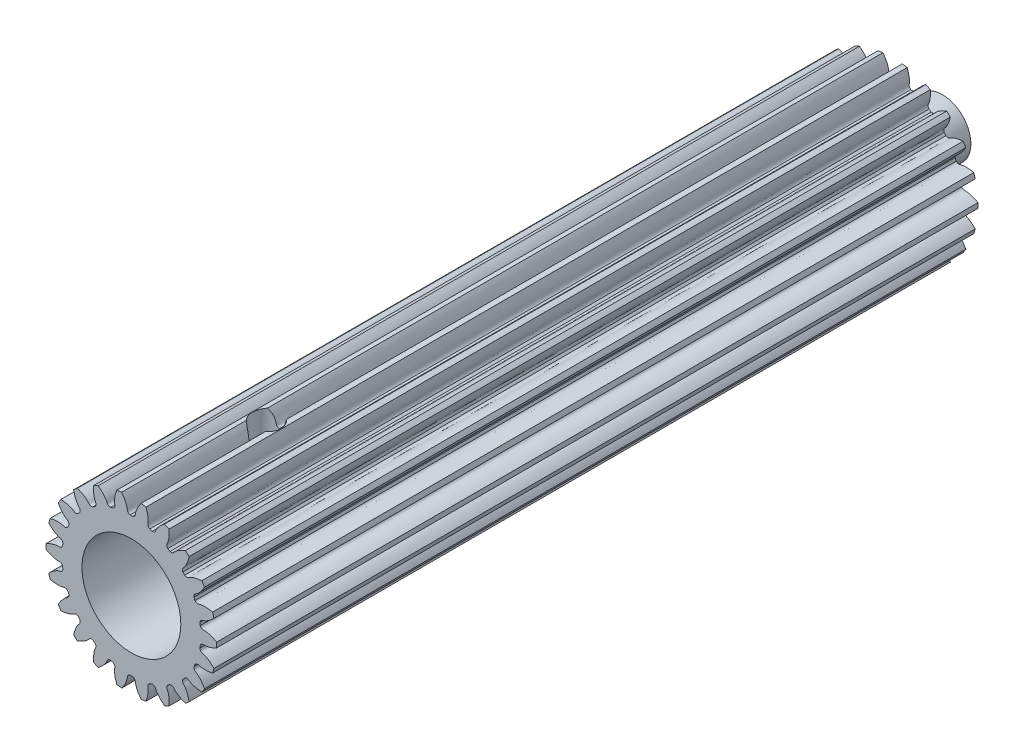
SolidWorks part; units mm, degrees
ref_plane "前视基准面" through (0, 0, 0) normal (0, 0, 1) x (1, 0, 0)
ref_plane "上视基准面" through (0, 0, 0) normal (0, 1, 0) x (1, 0, 0)
ref_plane "右视基准面" through (0, 0, 0) normal (1, 0, 0) x (0, 0, -1)
sketch "草图1" plane through (0, 0, 0) normal (0, 0, 1) x (1, 0, 0)
  circle A0 centre (0, 0) radius 12
extrude "凸台-拉伸1" add sketch "草图1" along normal blind 30
ref_axis "基准轴1" through (0, 0, -1.5) along (0, 0, 1)
sketch "草图2" plane through (0, 0, 0) normal (0, 0, 1) x (1, 0, 0)
  line L0 (0, 0) -> (0, 12) construction
  circle A0 centre (0, 0) radius 12 construction
  arc A1 (0.1857, 9.7482) -> (-0.1857, 9.7482) centre (0, 0) ccw
  arc A2 (3.0856, 13.5599) -> (-3.0856, 13.5599) centre (0, 0) ccw
  spline S0 degree 3 poles (0.1857, 9.7482) (0.5882, 9.8762) (0.5483, 10.1518) (0.5996, 10.4216) (0.606, 10.4519) (0.6139, 10.4862) (0.6235, 10.5243) (0.6349, 10.5661) (0.6484, 10.6117) (0.664, 10.661) (0.6819, 10.7139) (0.7023, 10.7703) (0.7253, 10.8301) (0.7511, 10.8933) (0.7797, 10.9597) (0.8114, 11.0293) (0.8462, 11.1021) (0.8843, 11.1778) (0.9259, 11.2563) (0.9711, 11.3377) (1.0199, 11.4217) (1.0726, 11.5082) (1.1292, 11.5972) (1.1899, 11.6884) (1.2547, 11.7818) (1.3238, 11.8773) (1.3973, 11.9746) (1.4753, 12.0737) (1.5579, 12.1744) (1.6452, 12.2766) (1.7372, 12.3802) (1.8341, 12.4849) (1.9359, 12.5906) (2.0428, 12.6972) (2.1547, 12.8044) (2.2718, 12.9123) (2.3942, 13.0205) (2.5218, 13.1289) (2.6548, 13.2373) (2.8415, 13.3834) (2.9864, 13.49) (3.0856, 13.5599) knots 0 0 0 0 0.157021 0.162531 0.168888 0.176093 0.184146 0.193046 0.202794 0.213389 0.224833 0.237123 0.250262 0.264248 0.279082 0.294763 0.311292 0.328669 0.346893 0.365965 0.385884 0.406652 0.428266 0.450729 0.474039 0.498197 0.523202 0.549055 0.575756 0.603304 0.6317 0.660944 0.691035 0.721974 0.75376 0.786395 0.819876 0.854206 0.889383 0.925408 1 1 1 1
  spline S1 degree 3 poles (-0.1857, 9.7482) (-0.5882, 9.8762) (-0.5483, 10.1518) (-0.5996, 10.4216) (-0.606, 10.4519) (-0.6139, 10.4862) (-0.6235, 10.5243) (-0.6349, 10.5661) (-0.6484, 10.6117) (-0.664, 10.661) (-0.6819, 10.7139) (-0.7023, 10.7703) (-0.7253, 10.8301) (-0.7511, 10.8933) (-0.7797, 10.9597) (-0.8114, 11.0293) (-0.8462, 11.1021) (-0.8843, 11.1778) (-0.9259, 11.2563) (-0.9711, 11.3377) (-1.0199, 11.4217) (-1.0726, 11.5082) (-1.1292, 11.5972) (-1.1899, 11.6884) (-1.2547, 11.7818) (-1.3238, 11.8773) (-1.3973, 11.9746) (-1.4753, 12.0737) (-1.5579, 12.1744) (-1.6452, 12.2766) (-1.7372, 12.3802) (-1.8341, 12.4849) (-1.9359, 12.5906) (-2.0428, 12.6972) (-2.1547, 12.8044) (-2.2718, 12.9123) (-2.3942, 13.0205) (-2.5218, 13.1289) (-2.6548, 13.2373) (-2.8415, 13.3834) (-2.9864, 13.49) (-3.0856, 13.5599) knots 0 0 0 0 0.157021 0.162531 0.168888 0.176093 0.184146 0.193046 0.202794 0.213389 0.224833 0.237123 0.250262 0.264248 0.279082 0.294763 0.311292 0.328669 0.346893 0.365965 0.385884 0.406652 0.428266 0.450729 0.474039 0.498197 0.523202 0.549055 0.575756 0.603304 0.6317 0.660944 0.691035 0.721974 0.75376 0.786395 0.819876 0.854206 0.889383 0.925408 1 1 1 1
extrude "切除-拉伸1" cut sketch "草图2" along normal through all
pattern_circular "阵列(圆周)1" count 22 every 16.364 about axis through (0, 0, -1.5) along (0, 0, 1) of "切除-拉伸1"
sketch "草图3" plane through (0, 0, 0) normal (0, 0, 1) x (1, 0, 0)
  circle A0 centre (0, 0) radius 11 construction
  dimension "Dn" = 22
sketch "草图4" plane through (0, 0, 0) normal (0, 0, -1) x (-1, 0, 0)
  arc A45 (2.9245, 9.3011) -> (2.5682, 9.4057) centre (0, 0) ccw
  arc A46 (2.0557, 11.8226) -> (1.3584, 11.9229) centre (0, 0) ccw
  arc A47 (0.1857, 9.7482) -> (-0.1857, 9.7482) centre (0, 0) ccw
  arc A48 (-1.3584, 11.9229) -> (-2.0557, 11.8226) centre (0, 0) ccw
  arc A49 (-2.5682, 9.4057) -> (-2.9245, 9.3011) centre (0, 0) ccw
  arc A50 (-4.6624, 11.0572) -> (-5.3032, 10.7646) centre (0, 0) ccw
  arc A51 (-5.1141, 8.3011) -> (-5.4265, 8.1004) centre (0, 0) ccw
  arc A52 (-7.5887, 9.2958) -> (-8.1211, 8.8344) centre (0, 0) ccw
  arc A53 (-7.2456, 6.5241) -> (-7.4888, 6.2434) centre (0, 0) ccw
  arc A54 (-9.9003, 6.7812) -> (-10.2811, 6.1886) centre (0, 0) ccw
  arc A55 (-8.7902, 4.2184) -> (-8.9444, 3.8807) centre (0, 0) ccw
  arc A56 (-11.4097, 3.7173) -> (-11.6082, 3.0414) centre (0, 0) ccw
  arc A57 (-9.6226, 1.5711) -> (-9.6754, 1.2035) centre (0, 0) ccw
  arc A58 (-11.9948, 0.3522) -> (-11.9948, -0.3522) centre (0, 0) ccw
  arc A59 (-9.6754, -1.2035) -> (-9.6226, -1.5711) centre (0, 0) ccw
  arc A60 (-11.6082, -3.0414) -> (-11.4097, -3.7173) centre (0, 0) ccw
  arc A61 (-8.9444, -3.8807) -> (-8.7902, -4.2184) centre (0, 0) ccw
  arc A62 (-10.2811, -6.1886) -> (-9.9003, -6.7812) centre (0, 0) ccw
  arc A63 (-7.4888, -6.2434) -> (-7.2456, -6.5241) centre (0, 0) ccw
  arc A64 (-8.1211, -8.8344) -> (-7.5887, -9.2958) centre (0, 0) ccw
  arc A65 (-5.4265, -8.1004) -> (-5.1141, -8.3011) centre (0, 0) ccw
  arc A66 (-5.3032, -10.7646) -> (-4.6624, -11.0572) centre (0, 0) ccw
  arc A67 (-2.9245, -9.3011) -> (-2.5682, -9.4057) centre (0, 0) ccw
  arc A68 (-2.0557, -11.8226) -> (-1.3584, -11.9229) centre (0, 0) ccw
  arc A69 (-0.1857, -9.7482) -> (0.1857, -9.7482) centre (0, 0) ccw
  arc A70 (1.3584, -11.9229) -> (2.0557, -11.8226) centre (0, 0) ccw
  arc A71 (2.5682, -9.4057) -> (2.9245, -9.3011) centre (0, 0) ccw
  arc A72 (4.6624, -11.0572) -> (5.3032, -10.7646) centre (0, 0) ccw
  arc A73 (5.1141, -8.3011) -> (5.4265, -8.1004) centre (0, 0) ccw
  arc A74 (7.5887, -9.2958) -> (8.1211, -8.8344) centre (0, 0) ccw
  arc A75 (7.2456, -6.5241) -> (7.4888, -6.2434) centre (0, 0) ccw
  arc A76 (9.9003, -6.7812) -> (10.2811, -6.1886) centre (0, 0) ccw
  arc A77 (8.7902, -4.2184) -> (8.9444, -3.8807) centre (0, 0) ccw
  arc A78 (11.4097, -3.7173) -> (11.6082, -3.0414) centre (0, 0) ccw
  arc A79 (9.6226, -1.5711) -> (9.6754, -1.2035) centre (0, 0) ccw
  arc A80 (11.9948, -0.3522) -> (11.9948, 0.3522) centre (0, 0) ccw
  arc A81 (9.6754, 1.2035) -> (9.6226, 1.5711) centre (0, 0) ccw
  arc A82 (11.6082, 3.0414) -> (11.4097, 3.7173) centre (0, 0) ccw
  arc A83 (8.9444, 3.8807) -> (8.7902, 4.2184) centre (0, 0) ccw
  arc A84 (10.2811, 6.1886) -> (9.9003, 6.7812) centre (0, 0) ccw
  arc A85 (7.4888, 6.2434) -> (7.2456, 6.5241) centre (0, 0) ccw
  arc A86 (8.1211, 8.8344) -> (7.5887, 9.2958) centre (0, 0) ccw
  arc A87 (5.4265, 8.1004) -> (5.1141, 8.3011) centre (0, 0) ccw
  arc A88 (5.3032, 10.7646) -> (4.6624, 11.0572) centre (0, 0) ccw
  arc A89 (2.9245, 9.3011) -> (2.5682, 9.4057) centre (0, 0) ccw
  arc A90 (2.0557, 11.8226) -> (1.3584, 11.9229) centre (0, 0) ccw
  arc A91 (0.1857, 9.7482) -> (-0.1857, 9.7482) centre (0, 0) ccw
  arc A92 (-1.3584, 11.9229) -> (-2.0557, 11.8226) centre (0, 0) ccw
  arc A93 (-2.5682, 9.4057) -> (-2.9245, 9.3011) centre (0, 0) ccw
  arc A94 (-4.6624, 11.0572) -> (-5.3032, 10.7646) centre (0, 0) ccw
  arc A95 (-5.1141, 8.3011) -> (-5.4265, 8.1004) centre (0, 0) ccw
  arc A96 (-7.5887, 9.2958) -> (-8.1211, 8.8344) centre (0, 0) ccw
  arc A97 (-7.2456, 6.5241) -> (-7.4888, 6.2434) centre (0, 0) ccw
  arc A98 (-9.9003, 6.7812) -> (-10.2811, 6.1886) centre (0, 0) ccw
  arc A99 (-8.7902, 4.2184) -> (-8.9444, 3.8807) centre (0, 0) ccw
  arc A100 (-11.4097, 3.7173) -> (-11.6082, 3.0414) centre (0, 0) ccw
  arc A101 (-9.6226, 1.5711) -> (-9.6754, 1.2035) centre (0, 0) ccw
  arc A102 (-11.9948, 0.3522) -> (-11.9948, -0.3522) centre (0, 0) ccw
  arc A103 (-9.6754, -1.2035) -> (-9.6226, -1.5711) centre (0, 0) ccw
  arc A104 (-11.6082, -3.0414) -> (-11.4097, -3.7173) centre (0, 0) ccw
  arc A105 (-8.9444, -3.8807) -> (-8.7902, -4.2184) centre (0, 0) ccw
  arc A106 (-10.2811, -6.1886) -> (-9.9003, -6.7812) centre (0, 0) ccw
  arc A107 (-7.4888, -6.2434) -> (-7.2456, -6.5241) centre (0, 0) ccw
  arc A108 (-8.1211, -8.8344) -> (-7.5887, -9.2958) centre (0, 0) ccw
  arc A109 (-5.4265, -8.1004) -> (-5.1141, -8.3011) centre (0, 0) ccw
  arc A110 (-5.3032, -10.7646) -> (-4.6624, -11.0572) centre (0, 0) ccw
  arc A111 (-2.9245, -9.3011) -> (-2.5682, -9.4057) centre (0, 0) ccw
  arc A112 (-2.0557, -11.8226) -> (-1.3584, -11.9229) centre (0, 0) ccw
  arc A113 (-0.1857, -9.7482) -> (0.1857, -9.7482) centre (0, 0) ccw
  arc A114 (1.3584, -11.9229) -> (2.0557, -11.8226) centre (0, 0) ccw
  arc A115 (2.5682, -9.4057) -> (2.9245, -9.3011) centre (0, 0) ccw
  arc A116 (4.6624, -11.0572) -> (5.3032, -10.7646) centre (0, 0) ccw
  arc A117 (5.1141, -8.3011) -> (5.4265, -8.1004) centre (0, 0) ccw
  arc A118 (7.5887, -9.2958) -> (8.1211, -8.8344) centre (0, 0) ccw
  arc A119 (7.2456, -6.5241) -> (7.4888, -6.2434) centre (0, 0) ccw
  arc A120 (9.9003, -6.7812) -> (10.2811, -6.1886) centre (0, 0) ccw
  arc A121 (8.7902, -4.2184) -> (8.9444, -3.8807) centre (0, 0) ccw
  arc A122 (11.4097, -3.7173) -> (11.6082, -3.0414) centre (0, 0) ccw
  arc A123 (9.6226, -1.5711) -> (9.6754, -1.2035) centre (0, 0) ccw
  arc A124 (11.9948, -0.3522) -> (11.9948, 0.3522) centre (0, 0) ccw
  arc A125 (9.6754, 1.2035) -> (9.6226, 1.5711) centre (0, 0) ccw
  arc A126 (11.6082, 3.0414) -> (11.4097, 3.7173) centre (0, 0) ccw
  arc A127 (8.9444, 3.8807) -> (8.7902, 4.2184) centre (0, 0) ccw
  arc A128 (10.2811, 6.1886) -> (9.9003, 6.7812) centre (0, 0) ccw
  arc A129 (7.4888, 6.2434) -> (7.2456, 6.5241) centre (0, 0) ccw
  arc A130 (8.1211, 8.8344) -> (7.5887, 9.2958) centre (0, 0) ccw
  arc A131 (5.4265, 8.1004) -> (5.1141, 8.3011) centre (0, 0) ccw
  arc A132 (5.3032, 10.7646) -> (4.6624, 11.0572) centre (0, 0) ccw
  spline S44 degree 3 poles (-6562.0363, 2433.3447) (210.1462, -143.3518) (27.5625, 30.6747) (4.2738, 10.7434) (4.1283, 10.6084) (3.9999, 10.4794) (3.888, 10.3576) (3.7917, 10.2441) (3.7102, 10.1398) (3.6518, 10.0587) (3.6037, 9.9872) (3.5713, 9.9359) (3.5381, 9.8795) (3.5167, 9.8409) (0.7608, 4.4593) (40.1108, -21.8996) (-5890.5321, 3783.681) knots -18.214825 -18.214825 -18.214825 -18.214825 0.549271 0.593348 0.634035 0.671331 0.705237 0.735752 0.762877 0.786611 0.797206 0.815854 0.823907 0.837469 0.842979 4.542303 4.542303 4.542303 4.542303 only from (4.6624, 11.0572) to (2.9245, 9.3011)
  spline S45 degree 3 poles (6999.9868, -1.6264) (-45.5784, 3.2625) (1.7708, 4.163) (2.3619, 10.18) (2.3658, 10.2385) (2.3681, 10.3211) (2.3668, 10.4204) (2.3608, 10.536) (2.3486, 10.6678) (2.329, 10.8154) (2.3007, 10.9784) (2.2624, 11.1562) (2.213, 11.3485) (2.1511, 11.5544) (-8.4551, 42.3513) (-266.8007, -17.8123) (6842.6381, -1469.6189) knots -3.542118 -3.542118 -3.542118 -3.542118 0.157021 0.162531 0.176093 0.193046 0.213389 0.237123 0.264248 0.294763 0.328669 0.365965 0.406652 0.450729 0.498197 20.435356 20.435356 20.435356 20.435356 only from (2.5682, 9.4057) to (2.0557, 11.8226)
  spline S46 degree 3 poles (-6981.7801, 486.0379) (242.0207, -78.34) (17.804, 37.1975) (1.0739, 11.5123) (0.9723, 11.3417) (0.8855, 11.1818) (0.8124, 11.0334) (0.752, 10.8973) (0.7032, 10.7743) (0.6701, 10.6801) (0.644, 10.5979) (0.6274, 10.5396) (0.6113, 10.4761) (0.6018, 10.4331) (-0.5263, 4.493) (44.6558, -9.712) (-6717.9103, 1970.8607) knots -18.214825 -18.214825 -18.214825 -18.214825 0.549271 0.593348 0.634035 0.671331 0.705237 0.735752 0.762877 0.786611 0.797206 0.815854 0.823907 0.837469 0.842979 4.542303 4.542303 4.542303 4.542303 only from (1.3584, 11.9229) to (0.1857, 9.7482)
  spline S47 degree 3 poles (6716.8964, 1970.5637) (-44.6513, -9.7106) (0.5262, 4.4933) (-0.6018, 10.4331) (-0.6145, 10.4903) (-0.6356, 10.5702) (-0.6648, 10.6651) (-0.7032, 10.7743) (-0.752, 10.8973) (-0.8124, 11.0334) (-0.8855, 11.1818) (-0.9723, 11.3417) (-1.0739, 11.5123) (-1.1913, 11.6924) (-20.0444, 38.2537) (-250.9751, -92.2573) (6979.5027, 517.7049) knots -3.542118 -3.542118 -3.542118 -3.542118 0.157021 0.162531 0.176093 0.193046 0.213389 0.237123 0.264248 0.294763 0.328669 0.365965 0.406652 0.450729 0.498197 20.435356 20.435356 20.435356 20.435356 only from (-0.1857, 9.7482) to (-1.3584, 11.9229)
  spline S48 degree 3 poles (-6835.9017, -1500.6448) (254.2881, -6.9816) (6.6031, 40.7067) (-2.213, 11.3485) (-2.2624, 11.1562) (-2.3007, 10.9784) (-2.329, 10.8154) (-2.3486, 10.6678) (-2.3608, 10.536) (-2.366, 10.4362) (-2.3678, 10.3501) (-2.3674, 10.2894) (-2.3649, 10.224) (-2.3619, 10.18) (-1.7708, 4.1627) (45.5832, 3.2624) (-7001.0433, -1.6271) knots -18.214825 -18.214825 -18.214825 -18.214825 0.549271 0.593348 0.634035 0.671331 0.705237 0.735752 0.762877 0.786611 0.797206 0.815854 0.823907 0.837469 0.842979 4.542303 4.542303 4.542303 4.542303 only from (-2.0557, 11.8226) to (-2.5682, 9.4057)
  spline S49 degree 3 poles (5889.6429, 3783.1104) (-40.1068, -21.897) (-0.761, 4.4596) (-3.5167, 9.8409) (-3.5451, 9.8922) (-3.5879, 9.963) (-3.6426, 10.0458) (-3.7102, 10.1398) (-3.7917, 10.2441) (-3.888, 10.3576) (-3.9999, 10.4794) (-4.1283, 10.6084) (-4.2738, 10.7434) (-4.4372, 10.8832) (-30.0098, 31.057) (-214.817, -159.2281) (6550.9294, 2463.0873) knots -3.542118 -3.542118 -3.542118 -3.542118 0.157021 0.162531 0.176093 0.193046 0.213389 0.237123 0.264248 0.294763 0.328669 0.365965 0.406652 0.450729 0.498197 20.435356 20.435356 20.435356 20.435356 only from (-2.9245, 9.3011) to (-4.6624, 11.0572)
  spline S50 degree 3 poles (-6136.2191, -3365.7542) (245.9546, 64.9425) (-5.1328, 40.918) (-5.3206, 10.2653) (-5.3138, 10.0669) (-5.3004, 9.8855) (-5.2817, 9.7211) (-5.2589, 9.574) (-5.2335, 9.4441) (-5.2104, 9.3469) (-5.1879, 9.2637) (-5.1704, 9.2057) (-5.1495, 9.1436) (-5.1343, 9.1022) (-2.8719, 3.4952) (42.8176, 15.9725) (-6716.9935, -1973.983) knots -18.214825 -18.214825 -18.214825 -18.214825 0.549271 0.593348 0.634035 0.671331 0.705237 0.735752 0.762877 0.786611 0.797206 0.815854 0.823907 0.837469 0.842979 4.542303 4.542303 4.542303 4.542303 only from (-5.3032, 10.7646) to (-5.1141, 8.3011)
  spline S51 degree 3 poles (4585.2456, 5289.172) (-32.3131, -32.3094) (-1.9866, 4.0645) (-6.1468, 8.4515) (-6.1884, 8.4928) (-6.2494, 8.5486) (-6.3253, 8.6126) (-6.4166, 8.6838) (-6.5242, 8.7609) (-6.6486, 8.8427) (-6.7903, 8.928) (-6.9498, 9.0156) (-7.1274, 9.1041) (-7.3236, 9.1923) (-37.5439, 21.3442) (-161.2557, -213.2991) (5591.6389, 4208.9251) knots -3.542118 -3.542118 -3.542118 -3.542118 0.157021 0.162531 0.176093 0.193046 0.213389 0.237123 0.264248 0.294763 0.328669 0.365965 0.406652 0.450729 0.498197 20.435356 20.435356 20.435356 20.435356 only from (-5.4265, 8.1004) to (-7.5887, 9.2958)
  spline S52 degree 3 poles (-4939.4166, -4958.1902) (217.6953, 131.6052) (-16.4528, 37.8145) (-7.9971, 8.3505) (-7.9348, 8.1621) (-7.8708, 7.9917) (-7.8065, 7.8393) (-7.7432, 7.7046) (-7.6822, 7.5871) (-7.6327, 7.5003) (-7.5876, 7.4269) (-7.5545, 7.3761) (-7.517, 7.3224) (-7.4907, 7.287) (-3.7403, 2.5445) (36.5832, 27.3886) (-5888.7728, -3786.4186) knots -18.214825 -18.214825 -18.214825 -18.214825 0.549271 0.593348 0.634035 0.671331 0.705237 0.735752 0.762877 0.786611 0.797206 0.815854 0.823907 0.837469 0.842979 4.542303 4.542303 4.542303 4.542303 only from (-8.1211, 8.8344) to (-7.2456, 6.5241)
  spline S53 degree 3 poles (2909.379, 6366.7364) (-21.9016, -40.1043) (-3.0512, 3.3402) (-8.2789, 6.3774) (-8.3304, 6.4053) (-8.4047, 6.4416) (-8.4955, 6.4817) (-8.6032, 6.5243) (-8.7281, 6.5679) (-8.8705, 6.6114) (-9.0305, 6.6533) (-9.2082, 6.6924) (-9.4036, 6.7273) (-9.6167, 6.7566) (-42.0365, 9.9023) (-94.6304, -250.09) (4179.347, 5613.7808) knots -3.542118 -3.542118 -3.542118 -3.542118 0.157021 0.162531 0.176093 0.193046 0.213389 0.237123 0.264248 0.294763 0.328669 0.365965 0.406652 0.450729 0.498197 20.435356 20.435356 20.435356 20.435356 only from (-7.4888, 6.2434) to (-9.9003, 6.7812)
  spline S54 degree 3 poles (-3342.4519, -6148.9431) (171.7996, 187.6062) (-26.44, 31.6475) (-10.0258, 5.7592) (-9.9129, 5.596) (-9.8035, 5.4506) (-9.6989, 5.3224) (-9.6002, 5.211) (-9.5086, 5.1155) (-9.4366, 5.0462) (-9.3727, 4.9884) (-9.3266, 4.949) (-9.2755, 4.908) (-9.2403, 4.8814) (-4.3056, 1.3877) (27.3851, 36.5859) (-4583.4787, -5292.101) knots -18.214825 -18.214825 -18.214825 -18.214825 0.549271 0.593348 0.634035 0.671331 0.705237 0.735752 0.762877 0.786611 0.797206 0.815854 0.823907 0.837469 0.842979 4.542303 4.542303 4.542303 4.542303 only from (-10.2811, 6.1886) to (-8.7902, 4.2184)
  spline S55 degree 3 poles (997.8118, 6928.5056) (-9.7158, -44.6502) (-3.8686, 2.3453) (-9.7402, 3.7867) (-9.7976, 3.7989) (-9.8791, 3.8128) (-9.9775, 3.8257) (-10.0928, 3.8362) (-10.225, 3.8429) (-10.3738, 3.8445) (-10.5392, 3.8396) (-10.7207, 3.8271) (-10.918, 3.8055) (-11.1307, 3.7736) (-43.1235, -2.3419) (-20.3387, -266.62) (2428.4693, 6563.8413) knots -3.542118 -3.542118 -3.542118 -3.542118 0.157021 0.162531 0.176093 0.193046 0.213389 0.237123 0.264248 0.294763 0.328669 0.365965 0.406652 0.450729 0.498197 20.435356 20.435356 20.435356 20.435356 only from (-8.9444, 3.8807) to (-11.4097, 3.7173)
  spline S56 degree 3 poles (-1474.7016, -6841.5453) (111.9857, 228.4083) (-34.2851, 22.9165) (-11.2422, 2.7013) (-11.0879, 2.5765) (-10.942, 2.4678) (-10.8055, 2.3743) (-10.6794, 2.2952) (-10.5646, 2.2294) (-10.476, 2.1832) (-10.3984, 2.1457) (-10.3431, 2.1209) (-10.2825, 2.096) (-10.2412, 2.0804) (-4.5222, 0.1185) (15.9684, 42.8191) (-2906.8585, -6369.0489) knots -18.214825 -18.214825 -18.214825 -18.214825 0.549271 0.593348 0.634035 0.671331 0.705237 0.735752 0.762877 0.786611 0.797206 0.815854 0.823907 0.837469 0.842979 4.542303 4.542303 4.542303 4.542303 only from (-11.6082, 3.0414) to (-9.6226, 1.5711)
  spline S57 degree 3 poles (-994.5922, 6928.9685) (3.2572, -45.5788) (-4.3727, 1.1604) (-10.4125, 0.8891) (-10.4709, 0.8847) (-10.5531, 0.8751) (-10.6512, 0.8598) (-10.7647, 0.8373) (-10.8934, 0.8065) (-11.0367, 0.7661) (-11.194, 0.7149) (-11.3647, 0.6517) (-11.5479, 0.5754) (-11.743, 0.4849) (-40.717, -14.3963) (55.6007, -261.5501) (480.8514, 6982.1385) knots -3.542118 -3.542118 -3.542118 -3.542118 0.157021 0.162531 0.176093 0.193046 0.213389 0.237123 0.264248 0.294763 0.328669 0.365965 0.406652 0.450729 0.498197 20.435356 20.435356 20.435356 20.435356 only from (-9.6754, 1.2035) to (-11.9948, 0.3522)
  spline S58 degree 3 poles (512.5202, -6979.8861) (43.0995, 250.7062) (-39.3526, 12.329) (-11.5479, -0.5754) (-11.3647, -0.6517) (-11.194, -0.7149) (-11.0367, -0.7661) (-10.8934, -0.8065) (-10.7647, -0.8373) (-10.6667, -0.8567) (-10.5817, -0.8708) (-10.5216, -0.879) (-10.4565, -0.8858) (-10.4125, -0.8891) (-4.3724, -1.1604) (3.258, 45.5835) (-994.7418, -6930.0144) knots -18.214825 -18.214825 -18.214825 -18.214825 0.549271 0.593348 0.634035 0.671331 0.705237 0.735752 0.762877 0.786611 0.797206 0.815854 0.823907 0.837469 0.842979 4.542303 4.542303 4.542303 4.542303 only from (-11.9948, -0.3522) to (-9.6754, -1.2035)
  spline S59 degree 3 poles (-2906.4202, 6368.0876) (15.9663, -42.8149) (-4.5225, -0.1186) (-10.2412, -2.0804) (-10.296, -2.1012) (-10.3722, -2.1335) (-10.4619, -2.1758) (-10.5646, -2.2294) (-10.6794, -2.2952) (-10.8055, -2.3743) (-10.942, -2.4678) (-11.0879, -2.5765) (-11.2422, -2.7014) (-11.4039, -2.8432) (-35.0117, -25.2845) (127.0357, -235.291) (-1505.7222, 6834.7843) knots -3.542118 -3.542118 -3.542118 -3.542118 0.157021 0.162531 0.176093 0.193046 0.213389 0.237123 0.264248 0.294763 0.328669 0.365965 0.406652 0.450729 0.498197 20.435356 20.435356 20.435356 20.435356 only from (-9.6226, -1.5711) to (-11.6082, -3.0414)
  spline S60 degree 3 poles (2458.2207, -6552.758) (-29.2785, 252.6934) (-41.232, 0.7427) (-10.918, -3.8055) (-10.7207, -3.8271) (-10.5392, -3.8396) (-10.3738, -3.8445) (-10.225, -3.8429) (-10.0928, -3.8362) (-9.9933, -3.8272) (-9.9078, -3.8167) (-9.8478, -3.8076) (-9.7834, -3.7958) (-9.7402, -3.7867) (-3.8684, -2.3452) (-9.7163, 44.6549) (997.9629, -6929.5512) knots -18.214825 -18.214825 -18.214825 -18.214825 0.549271 0.593348 0.634035 0.671331 0.705237 0.735752 0.762877 0.786611 0.797206 0.815854 0.823907 0.837469 0.842979 4.542303 4.542303 4.542303 4.542303 only from (-11.4097, -3.7173) to (-8.9444, -3.8807)
  spline S61 degree 3 poles (-4582.7874, 5291.3021) (27.3819, -36.5824) (-4.3059, -1.3879) (-9.2403, -4.8814) (-9.287, -4.9168) (-9.351, -4.9692) (-9.4251, -5.0352) (-9.5086, -5.1155) (-9.6002, -5.211) (-9.6989, -5.3224) (-9.8035, -5.4506) (-9.9129, -5.596) (-10.0258, -5.7592) (-10.1409, -5.9408) (-26.4701, -34.1242) (188.179, -189.9699) (-3370.3111, 6133.7165) knots -3.542118 -3.542118 -3.542118 -3.542118 0.157021 0.162531 0.176093 0.193046 0.213389 0.237123 0.264248 0.294763 0.328669 0.365965 0.406652 0.450729 0.498197 20.435356 20.435356 20.435356 20.435356 only from (-8.7902, -4.2184) to (-10.2811, -6.1886)
  spline S62 degree 3 poles (4204.7707, -5594.7645) (-99.2844, 234.2088) (-39.7711, -10.9038) (-9.4036, -6.7273) (-9.2082, -6.6924) (-9.0305, -6.6533) (-8.8705, -6.6114) (-8.7281, -6.5679) (-8.6032, -6.5243) (-8.5102, -6.4876) (-8.4311, -6.4535) (-8.3761, -6.4279) (-8.3177, -6.3984) (-8.2789, -6.3774) (-3.0509, -3.3401) (-21.9035, 40.1087) (2909.8186, -6367.6971) knots -18.214825 -18.214825 -18.214825 -18.214825 0.549271 0.593348 0.634035 0.671331 0.705237 0.735752 0.762877 0.786611 0.797206 0.815854 0.823907 0.837469 0.842979 4.542303 4.542303 4.542303 4.542303 only from (-9.9003, -6.7812) to (-7.4888, -6.2434)
  spline S63 degree 3 poles (-5887.8844, 3785.8468) (36.5792, -27.3861) (-3.7404, -2.5448) (-7.4907, -7.287) (-7.5256, -7.3341) (-7.5722, -7.4024) (-7.6248, -7.4866) (-7.6822, -7.5871) (-7.7432, -7.7046) (-7.8065, -7.8393) (-7.8708, -7.9917) (-7.9348, -8.1621) (-7.9971, -8.3505) (-8.0564, -8.5572) (-15.7839, -40.1994) (234.0771, -129.2587) (-4961.8575, 4935.7316) knots -3.542118 -3.542118 -3.542118 -3.542118 0.157021 0.162531 0.176093 0.193046 0.213389 0.237123 0.264248 0.294763 0.328669 0.365965 0.406652 0.450729 0.498197 20.435356 20.435356 20.435356 20.435356 only from (-7.2456, -6.5241) to (-8.1211, -8.8344)
  spline S64 degree 3 poles (5610.6753, -4183.5164) (-161.247, 196.7501) (-35.0881, -21.6669) (-7.1274, -9.1041) (-6.9498, -9.0156) (-6.7903, -8.928) (-6.6486, -8.8427) (-6.5242, -8.7609) (-6.4166, -8.6838) (-6.3378, -8.6224) (-6.2715, -8.5674) (-6.2259, -8.5273) (-6.1781, -8.4826) (-6.1468, -8.4515) (-1.9864, -4.0643) (-32.3162, 32.313) (4585.938, -5289.97) knots -18.214825 -18.214825 -18.214825 -18.214825 0.549271 0.593348 0.634035 0.671331 0.705237 0.735752 0.762877 0.786611 0.797206 0.815854 0.823907 0.837469 0.842979 4.542303 4.542303 4.542303 4.542303 only from (-7.5887, -9.2958) to (-5.4265, -8.1004)
  spline S65 degree 3 poles (-6715.98, 1973.6847) (42.813, -15.9713) (-2.872, -3.4955) (-5.1343, -9.1022) (-5.1545, -9.1572) (-5.18, -9.2359) (-5.2067, -9.3315) (-5.2335, -9.4441) (-5.2589, -9.574) (-5.2817, -9.7211) (-5.3004, -9.8855) (-5.3138, -10.0669) (-5.3206, -10.2653) (-5.3192, -10.4804) (-3.8191, -43.0179) (261.0117, -58.0756) (-6151.4237, 3337.8829) knots -3.542118 -3.542118 -3.542118 -3.542118 0.157021 0.162531 0.176093 0.193046 0.213389 0.237123 0.264248 0.294763 0.328669 0.365965 0.406652 0.450729 0.498197 20.435356 20.435356 20.435356 20.435356 only from (-5.1141, -8.3011) to (-5.3032, -10.7646)
  spline S66 degree 3 poles (6562.0363, -2433.3447) (-210.1462, 143.3518) (-27.5625, -30.6747) (-4.2738, -10.7434) (-4.1283, -10.6084) (-3.9999, -10.4794) (-3.888, -10.3576) (-3.7917, -10.2441) (-3.7102, -10.1398) (-3.6518, -10.0587) (-3.6037, -9.9872) (-3.5713, -9.9359) (-3.5381, -9.8795) (-3.5167, -9.8409) (-0.7608, -4.4593) (-40.1108, 21.8996) (5890.5321, -3783.681) knots -18.214825 -18.214825 -18.214825 -18.214825 0.549271 0.593348 0.634035 0.671331 0.705237 0.735752 0.762877 0.786611 0.797206 0.815854 0.823907 0.837469 0.842979 4.542303 4.542303 4.542303 4.542303 only from (-4.6624, -11.0572) to (-2.9245, -9.3011)
  spline S67 degree 3 poles (-6999.9868, 1.6264) (45.5784, -3.2625) (-1.7708, -4.163) (-2.3619, -10.18) (-2.3658, -10.2385) (-2.3681, -10.3211) (-2.3668, -10.4204) (-2.3608, -10.536) (-2.3486, -10.6678) (-2.329, -10.8154) (-2.3007, -10.9784) (-2.2624, -11.1562) (-2.213, -11.3485) (-2.1511, -11.5544) (8.4551, -42.3513) (266.8007, 17.8123) (-6842.6381, 1469.6189) knots -3.542118 -3.542118 -3.542118 -3.542118 0.157021 0.162531 0.176093 0.193046 0.213389 0.237123 0.264248 0.294763 0.328669 0.365965 0.406652 0.450729 0.498197 20.435356 20.435356 20.435356 20.435356 only from (-2.5682, -9.4057) to (-2.0557, -11.8226)
  spline S68 degree 3 poles (6981.7801, -486.0379) (-242.0207, 78.34) (-17.804, -37.1975) (-1.0739, -11.5123) (-0.9723, -11.3417) (-0.8855, -11.1818) (-0.8124, -11.0334) (-0.752, -10.8973) (-0.7032, -10.7743) (-0.6701, -10.6801) (-0.644, -10.5979) (-0.6274, -10.5396) (-0.6113, -10.4761) (-0.6018, -10.4331) (0.5263, -4.493) (-44.6558, 9.712) (6717.9103, -1970.8607) knots -18.214825 -18.214825 -18.214825 -18.214825 0.549271 0.593348 0.634035 0.671331 0.705237 0.735752 0.762877 0.786611 0.797206 0.815854 0.823907 0.837469 0.842979 4.542303 4.542303 4.542303 4.542303 only from (-1.3584, -11.9229) to (-0.1857, -9.7482)
  spline S69 degree 3 poles (-6716.8964, -1970.5637) (44.6513, 9.7106) (-0.5262, -4.4933) (0.6018, -10.4331) (0.6145, -10.4903) (0.6356, -10.5702) (0.6648, -10.6651) (0.7032, -10.7743) (0.752, -10.8973) (0.8124, -11.0334) (0.8855, -11.1818) (0.9723, -11.3417) (1.0739, -11.5123) (1.1913, -11.6924) (20.0444, -38.2537) (250.9751, 92.2573) (-6979.5027, -517.7049) knots -3.542118 -3.542118 -3.542118 -3.542118 0.157021 0.162531 0.176093 0.193046 0.213389 0.237123 0.264248 0.294763 0.328669 0.365965 0.406652 0.450729 0.498197 20.435356 20.435356 20.435356 20.435356 only from (0.1857, -9.7482) to (1.3584, -11.9229)
  spline S70 degree 3 poles (6835.9017, 1500.6448) (-254.2881, 6.9816) (-6.6031, -40.7067) (2.213, -11.3485) (2.2624, -11.1562) (2.3007, -10.9784) (2.329, -10.8154) (2.3486, -10.6678) (2.3608, -10.536) (2.366, -10.4362) (2.3678, -10.3501) (2.3674, -10.2894) (2.3649, -10.224) (2.3619, -10.18) (1.7708, -4.1627) (-45.5832, -3.2624) (7001.0433, 1.6271) knots -18.214825 -18.214825 -18.214825 -18.214825 0.549271 0.593348 0.634035 0.671331 0.705237 0.735752 0.762877 0.786611 0.797206 0.815854 0.823907 0.837469 0.842979 4.542303 4.542303 4.542303 4.542303 only from (2.0557, -11.8226) to (2.5682, -9.4057)
  spline S71 degree 3 poles (-5889.6429, -3783.1104) (40.1068, 21.897) (0.761, -4.4596) (3.5167, -9.8409) (3.5451, -9.8922) (3.5879, -9.963) (3.6426, -10.0458) (3.7102, -10.1398) (3.7917, -10.2441) (3.888, -10.3576) (3.9999, -10.4794) (4.1283, -10.6084) (4.2738, -10.7434) (4.4372, -10.8832) (30.0098, -31.057) (214.817, 159.2281) (-6550.9294, -2463.0873) knots -3.542118 -3.542118 -3.542118 -3.542118 0.157021 0.162531 0.176093 0.193046 0.213389 0.237123 0.264248 0.294763 0.328669 0.365965 0.406652 0.450729 0.498197 20.435356 20.435356 20.435356 20.435356 only from (2.9245, -9.3011) to (4.6624, -11.0572)
  spline S72 degree 3 poles (6136.2191, 3365.7542) (-245.9546, -64.9425) (5.1328, -40.918) (5.3206, -10.2653) (5.3138, -10.0669) (5.3004, -9.8855) (5.2817, -9.7211) (5.2589, -9.574) (5.2335, -9.4441) (5.2104, -9.3469) (5.1879, -9.2637) (5.1704, -9.2057) (5.1495, -9.1436) (5.1343, -9.1022) (2.8719, -3.4952) (-42.8176, -15.9725) (6716.9935, 1973.983) knots -18.214825 -18.214825 -18.214825 -18.214825 0.549271 0.593348 0.634035 0.671331 0.705237 0.735752 0.762877 0.786611 0.797206 0.815854 0.823907 0.837469 0.842979 4.542303 4.542303 4.542303 4.542303 only from (5.3032, -10.7646) to (5.1141, -8.3011)
  spline S73 degree 3 poles (-4585.2456, -5289.172) (32.3131, 32.3094) (1.9866, -4.0645) (6.1468, -8.4515) (6.1884, -8.4928) (6.2494, -8.5486) (6.3253, -8.6126) (6.4166, -8.6838) (6.5242, -8.7609) (6.6486, -8.8427) (6.7903, -8.928) (6.9498, -9.0156) (7.1274, -9.1041) (7.3236, -9.1923) (37.5439, -21.3442) (161.2557, 213.2991) (-5591.6389, -4208.9251) knots -3.542118 -3.542118 -3.542118 -3.542118 0.157021 0.162531 0.176093 0.193046 0.213389 0.237123 0.264248 0.294763 0.328669 0.365965 0.406652 0.450729 0.498197 20.435356 20.435356 20.435356 20.435356 only from (5.4265, -8.1004) to (7.5887, -9.2958)
  spline S74 degree 3 poles (4939.4166, 4958.1902) (-217.6953, -131.6052) (16.4528, -37.8145) (7.9971, -8.3505) (7.9348, -8.1621) (7.8708, -7.9917) (7.8065, -7.8393) (7.7432, -7.7046) (7.6822, -7.5871) (7.6327, -7.5003) (7.5876, -7.4269) (7.5545, -7.3761) (7.517, -7.3224) (7.4907, -7.287) (3.7403, -2.5445) (-36.5832, -27.3886) (5888.7728, 3786.4186) knots -18.214825 -18.214825 -18.214825 -18.214825 0.549271 0.593348 0.634035 0.671331 0.705237 0.735752 0.762877 0.786611 0.797206 0.815854 0.823907 0.837469 0.842979 4.542303 4.542303 4.542303 4.542303 only from (8.1211, -8.8344) to (7.2456, -6.5241)
  spline S75 degree 3 poles (-2909.379, -6366.7364) (21.9016, 40.1043) (3.0512, -3.3402) (8.2789, -6.3774) (8.3304, -6.4053) (8.4047, -6.4416) (8.4955, -6.4817) (8.6032, -6.5243) (8.7281, -6.5679) (8.8705, -6.6114) (9.0305, -6.6533) (9.2082, -6.6924) (9.4036, -6.7273) (9.6167, -6.7566) (42.0365, -9.9023) (94.6304, 250.09) (-4179.347, -5613.7808) knots -3.542118 -3.542118 -3.542118 -3.542118 0.157021 0.162531 0.176093 0.193046 0.213389 0.237123 0.264248 0.294763 0.328669 0.365965 0.406652 0.450729 0.498197 20.435356 20.435356 20.435356 20.435356 only from (7.4888, -6.2434) to (9.9003, -6.7812)
  spline S76 degree 3 poles (3342.4519, 6148.9431) (-171.7996, -187.6062) (26.44, -31.6475) (10.0258, -5.7592) (9.9129, -5.596) (9.8035, -5.4506) (9.6989, -5.3224) (9.6002, -5.211) (9.5086, -5.1155) (9.4366, -5.0462) (9.3727, -4.9884) (9.3266, -4.949) (9.2755, -4.908) (9.2403, -4.8814) (4.3056, -1.3877) (-27.3851, -36.5859) (4583.4787, 5292.101) knots -18.214825 -18.214825 -18.214825 -18.214825 0.549271 0.593348 0.634035 0.671331 0.705237 0.735752 0.762877 0.786611 0.797206 0.815854 0.823907 0.837469 0.842979 4.542303 4.542303 4.542303 4.542303 only from (10.2811, -6.1886) to (8.7902, -4.2184)
  spline S77 degree 3 poles (-997.8118, -6928.5056) (9.7158, 44.6502) (3.8686, -2.3453) (9.7402, -3.7867) (9.7976, -3.7989) (9.8791, -3.8128) (9.9775, -3.8257) (10.0928, -3.8362) (10.225, -3.8429) (10.3738, -3.8445) (10.5392, -3.8396) (10.7207, -3.8271) (10.918, -3.8055) (11.1307, -3.7736) (43.1235, 2.3419) (20.3387, 266.62) (-2428.4693, -6563.8413) knots -3.542118 -3.542118 -3.542118 -3.542118 0.157021 0.162531 0.176093 0.193046 0.213389 0.237123 0.264248 0.294763 0.328669 0.365965 0.406652 0.450729 0.498197 20.435356 20.435356 20.435356 20.435356 only from (8.9444, -3.8807) to (11.4097, -3.7173)
  spline S78 degree 3 poles (1474.7016, 6841.5453) (-111.9857, -228.4083) (34.2851, -22.9165) (11.2422, -2.7013) (11.0879, -2.5765) (10.942, -2.4678) (10.8055, -2.3743) (10.6794, -2.2952) (10.5646, -2.2294) (10.476, -2.1832) (10.3984, -2.1457) (10.3431, -2.1209) (10.2825, -2.096) (10.2412, -2.0804) (4.5222, -0.1185) (-15.9684, -42.8191) (2906.8585, 6369.0489) knots -18.214825 -18.214825 -18.214825 -18.214825 0.549271 0.593348 0.634035 0.671331 0.705237 0.735752 0.762877 0.786611 0.797206 0.815854 0.823907 0.837469 0.842979 4.542303 4.542303 4.542303 4.542303 only from (11.6082, -3.0414) to (9.6226, -1.5711)
  spline S79 degree 3 poles (994.5922, -6928.9685) (-3.2572, 45.5788) (4.3727, -1.1604) (10.4125, -0.8891) (10.4709, -0.8847) (10.5531, -0.8751) (10.6512, -0.8598) (10.7647, -0.8373) (10.8934, -0.8065) (11.0367, -0.7661) (11.194, -0.7149) (11.3647, -0.6517) (11.5479, -0.5754) (11.743, -0.4849) (40.717, 14.3963) (-55.6007, 261.5501) (-480.8514, -6982.1385) knots -3.542118 -3.542118 -3.542118 -3.542118 0.157021 0.162531 0.176093 0.193046 0.213389 0.237123 0.264248 0.294763 0.328669 0.365965 0.406652 0.450729 0.498197 20.435356 20.435356 20.435356 20.435356 only from (9.6754, -1.2035) to (11.9948, -0.3522)
  spline S80 degree 3 poles (-512.5202, 6979.8861) (-43.0995, -250.7062) (39.3526, -12.329) (11.5479, 0.5754) (11.3647, 0.6517) (11.194, 0.7149) (11.0367, 0.7661) (10.8934, 0.8065) (10.7647, 0.8373) (10.6667, 0.8567) (10.5817, 0.8708) (10.5216, 0.879) (10.4565, 0.8858) (10.4125, 0.8891) (4.3724, 1.1604) (-3.258, -45.5835) (994.7418, 6930.0144) knots -18.214825 -18.214825 -18.214825 -18.214825 0.549271 0.593348 0.634035 0.671331 0.705237 0.735752 0.762877 0.786611 0.797206 0.815854 0.823907 0.837469 0.842979 4.542303 4.542303 4.542303 4.542303 only from (11.9948, 0.3522) to (9.6754, 1.2035)
  spline S81 degree 3 poles (2906.4202, -6368.0876) (-15.9663, 42.8149) (4.5225, 0.1186) (10.2412, 2.0804) (10.296, 2.1012) (10.3722, 2.1335) (10.4619, 2.1758) (10.5646, 2.2294) (10.6794, 2.2952) (10.8055, 2.3743) (10.942, 2.4678) (11.0879, 2.5765) (11.2422, 2.7014) (11.4039, 2.8432) (35.0117, 25.2845) (-127.0357, 235.291) (1505.7222, -6834.7843) knots -3.542118 -3.542118 -3.542118 -3.542118 0.157021 0.162531 0.176093 0.193046 0.213389 0.237123 0.264248 0.294763 0.328669 0.365965 0.406652 0.450729 0.498197 20.435356 20.435356 20.435356 20.435356 only from (9.6226, 1.5711) to (11.6082, 3.0414)
  spline S82 degree 3 poles (-2458.2207, 6552.758) (29.2785, -252.6934) (41.232, -0.7427) (10.918, 3.8055) (10.7207, 3.8271) (10.5392, 3.8396) (10.3738, 3.8445) (10.225, 3.8429) (10.0928, 3.8362) (9.9933, 3.8272) (9.9078, 3.8167) (9.8478, 3.8076) (9.7834, 3.7958) (9.7402, 3.7867) (3.8684, 2.3452) (9.7163, -44.6549) (-997.9629, 6929.5512) knots -18.214825 -18.214825 -18.214825 -18.214825 0.549271 0.593348 0.634035 0.671331 0.705237 0.735752 0.762877 0.786611 0.797206 0.815854 0.823907 0.837469 0.842979 4.542303 4.542303 4.542303 4.542303 only from (11.4097, 3.7173) to (8.9444, 3.8807)
  spline S83 degree 3 poles (4582.7874, -5291.3021) (-27.3819, 36.5824) (4.3059, 1.3879) (9.2403, 4.8814) (9.287, 4.9168) (9.351, 4.9692) (9.4251, 5.0352) (9.5086, 5.1155) (9.6002, 5.211) (9.6989, 5.3224) (9.8035, 5.4506) (9.9129, 5.596) (10.0258, 5.7592) (10.1409, 5.9408) (26.4701, 34.1242) (-188.179, 189.9699) (3370.3111, -6133.7165) knots -3.542118 -3.542118 -3.542118 -3.542118 0.157021 0.162531 0.176093 0.193046 0.213389 0.237123 0.264248 0.294763 0.328669 0.365965 0.406652 0.450729 0.498197 20.435356 20.435356 20.435356 20.435356 only from (8.7902, 4.2184) to (10.2811, 6.1886)
  spline S84 degree 3 poles (-4204.7707, 5594.7645) (99.2844, -234.2088) (39.7711, 10.9038) (9.4036, 6.7273) (9.2082, 6.6924) (9.0305, 6.6533) (8.8705, 6.6114) (8.7281, 6.5679) (8.6032, 6.5243) (8.5102, 6.4876) (8.4311, 6.4535) (8.3761, 6.4279) (8.3177, 6.3984) (8.2789, 6.3774) (3.0509, 3.3401) (21.9035, -40.1087) (-2909.8186, 6367.6971) knots -18.214825 -18.214825 -18.214825 -18.214825 0.549271 0.593348 0.634035 0.671331 0.705237 0.735752 0.762877 0.786611 0.797206 0.815854 0.823907 0.837469 0.842979 4.542303 4.542303 4.542303 4.542303 only from (9.9003, 6.7812) to (7.4888, 6.2434)
  spline S85 degree 3 poles (5887.8844, -3785.8468) (-36.5792, 27.3861) (3.7404, 2.5448) (7.4907, 7.287) (7.5256, 7.3341) (7.5722, 7.4024) (7.6248, 7.4866) (7.6822, 7.5871) (7.7432, 7.7046) (7.8065, 7.8393) (7.8708, 7.9917) (7.9348, 8.1621) (7.9971, 8.3505) (8.0564, 8.5572) (15.7839, 40.1994) (-234.0771, 129.2587) (4961.8575, -4935.7316) knots -3.542118 -3.542118 -3.542118 -3.542118 0.157021 0.162531 0.176093 0.193046 0.213389 0.237123 0.264248 0.294763 0.328669 0.365965 0.406652 0.450729 0.498197 20.435356 20.435356 20.435356 20.435356 only from (7.2456, 6.5241) to (8.1211, 8.8344)
  spline S86 degree 3 poles (-5610.6753, 4183.5164) (161.247, -196.7501) (35.0881, 21.6669) (7.1274, 9.1041) (6.9498, 9.0156) (6.7903, 8.928) (6.6486, 8.8427) (6.5242, 8.7609) (6.4166, 8.6838) (6.3378, 8.6224) (6.2715, 8.5674) (6.2259, 8.5273) (6.1781, 8.4826) (6.1468, 8.4515) (1.9864, 4.0643) (32.3162, -32.313) (-4585.938, 5289.97) knots -18.214825 -18.214825 -18.214825 -18.214825 0.549271 0.593348 0.634035 0.671331 0.705237 0.735752 0.762877 0.786611 0.797206 0.815854 0.823907 0.837469 0.842979 4.542303 4.542303 4.542303 4.542303 only from (7.5887, 9.2958) to (5.4265, 8.1004)
  spline S87 degree 3 poles (6715.98, -1973.6847) (-42.813, 15.9713) (2.872, 3.4955) (5.1343, 9.1022) (5.1545, 9.1572) (5.18, 9.2359) (5.2067, 9.3315) (5.2335, 9.4441) (5.2589, 9.574) (5.2817, 9.7211) (5.3004, 9.8855) (5.3138, 10.0669) (5.3206, 10.2653) (5.3192, 10.4804) (3.8191, 43.0179) (-261.0117, 58.0756) (6151.4237, -3337.8829) knots -3.542118 -3.542118 -3.542118 -3.542118 0.157021 0.162531 0.176093 0.193046 0.213389 0.237123 0.264248 0.294763 0.328669 0.365965 0.406652 0.450729 0.498197 20.435356 20.435356 20.435356 20.435356 only from (5.1141, 8.3011) to (5.3032, 10.7646)
  spline S88 degree 3 poles (4.6624, 11.0572) (4.5848, 10.9995) (4.452, 10.8959) (4.2738, 10.7434) (4.1283, 10.6084) (3.9999, 10.4794) (3.888, 10.3576) (3.7917, 10.2441) (3.7102, 10.1398) (3.6518, 10.0587) (3.6037, 9.9872) (3.5713, 9.9359) (3.5381, 9.8795) (3.5167, 9.8409) (3.3862, 9.5861) (3.3468, 9.3104) (2.9245, 9.3011) knots 0.48979 0.48979 0.48979 0.48979 0.549271 0.593348 0.634035 0.671331 0.705237 0.735752 0.762877 0.786611 0.797206 0.815854 0.823907 0.837469 0.842979 1 1 1 1
  spline S89 degree 3 poles (2.5682, 9.4057) (2.2181, 9.6418) (2.334, 9.895) (2.3619, 10.18) (2.3658, 10.2385) (2.3681, 10.3211) (2.3668, 10.4204) (2.3608, 10.536) (2.3486, 10.6678) (2.329, 10.8154) (2.3007, 10.9784) (2.2624, 11.1562) (2.213, 11.3485) (2.1511, 11.5544) (2.0963, 11.7137) (2.0626, 11.8043) (2.0557, 11.8226) knots 0 0 0 0 0.157021 0.162531 0.176093 0.193046 0.213389 0.237123 0.264248 0.294763 0.328669 0.365965 0.406652 0.450729 0.498197 0.51021 0.51021 0.51021 0.51021
  spline S90 degree 3 poles (1.3584, 11.9229) (1.3002, 11.8457) (1.2019, 11.7088) (1.0739, 11.5123) (0.9723, 11.3417) (0.8855, 11.1818) (0.8124, 11.0334) (0.752, 10.8973) (0.7032, 10.7743) (0.6701, 10.6801) (0.644, 10.5979) (0.6274, 10.5396) (0.6113, 10.4761) (0.6018, 10.4331) (0.5483, 10.1518) (0.5882, 9.8762) (0.1857, 9.7482) knots 0.48979 0.48979 0.48979 0.48979 0.549271 0.593348 0.634035 0.671331 0.705237 0.735752 0.762877 0.786611 0.797206 0.815854 0.823907 0.837469 0.842979 1 1 1 1
  spline S91 degree 3 poles (-0.1857, 9.7482) (-0.5882, 9.8762) (-0.5483, 10.1518) (-0.6018, 10.4331) (-0.6145, 10.4903) (-0.6356, 10.5702) (-0.6648, 10.6651) (-0.7032, 10.7743) (-0.752, 10.8973) (-0.8124, 11.0334) (-0.8855, 11.1818) (-0.9723, 11.3417) (-1.0739, 11.5123) (-1.1913, 11.6924) (-1.2888, 11.8298) (-1.3466, 11.9073) (-1.3584, 11.9229) knots 0 0 0 0 0.157021 0.162531 0.176093 0.193046 0.213389 0.237123 0.264248 0.294763 0.328669 0.365965 0.406652 0.450729 0.498197 0.51021 0.51021 0.51021 0.51021
  spline S92 degree 3 poles (-2.0557, 11.8226) (-2.0898, 11.7321) (-2.1455, 11.5732) (-2.213, 11.3485) (-2.2624, 11.1562) (-2.3007, 10.9784) (-2.329, 10.8154) (-2.3486, 10.6678) (-2.3608, 10.536) (-2.366, 10.4362) (-2.3678, 10.3501) (-2.3674, 10.2894) (-2.3649, 10.224) (-2.3619, 10.18) (-2.334, 9.895) (-2.2181, 9.6418) (-2.5682, 9.4057) knots 0.48979 0.48979 0.48979 0.48979 0.549271 0.593348 0.634035 0.671331 0.705237 0.735752 0.762877 0.786611 0.797206 0.815854 0.823907 0.837469 0.842979 1 1 1 1
  spline S93 degree 3 poles (-2.9245, 9.3011) (-3.3468, 9.3104) (-3.3862, 9.5861) (-3.5167, 9.8409) (-3.5451, 9.8922) (-3.5879, 9.963) (-3.6426, 10.0458) (-3.7102, 10.1398) (-3.7917, 10.2441) (-3.888, 10.3576) (-3.9999, 10.4794) (-4.1283, 10.6084) (-4.2738, 10.7434) (-4.4372, 10.8832) (-4.5694, 10.9875) (-4.6468, 11.0456) (-4.6624, 11.0572) knots 0 0 0 0 0.157021 0.162531 0.176093 0.193046 0.213389 0.237123 0.264248 0.294763 0.328669 0.365965 0.406652 0.450729 0.498197 0.51021 0.51021 0.51021 0.51021
  spline S94 degree 3 poles (-5.3032, 10.7646) (-5.3105, 10.6681) (-5.3191, 10.4999) (-5.3206, 10.2653) (-5.3138, 10.0669) (-5.3004, 9.8855) (-5.2817, 9.7211) (-5.2589, 9.574) (-5.2335, 9.4441) (-5.2104, 9.3469) (-5.1879, 9.2637) (-5.1704, 9.2057) (-5.1495, 9.1436) (-5.1343, 9.1022) (-5.0272, 8.8367) (-4.8447, 8.6264) (-5.1141, 8.3011) knots 0.48979 0.48979 0.48979 0.48979 0.549271 0.593348 0.634035 0.671331 0.705237 0.735752 0.762877 0.786611 0.797206 0.815854 0.823907 0.837469 0.842979 1 1 1 1
  spline S95 degree 3 poles (-5.4265, 8.1004) (-5.8343, 7.9904) (-5.9498, 8.2438) (-6.1468, 8.4515) (-6.1884, 8.4928) (-6.2494, 8.5486) (-6.3253, 8.6126) (-6.4166, 8.6838) (-6.5242, 8.7609) (-6.6486, 8.8427) (-6.7903, 8.928) (-6.9498, 9.0156) (-7.1274, 9.1041) (-7.3236, 9.1923) (-7.4798, 9.2551) (-7.5704, 9.289) (-7.5887, 9.2958) knots 0 0 0 0 0.157021 0.162531 0.176093 0.193046 0.213389 0.237123 0.264248 0.294763 0.328669 0.365965 0.406652 0.450729 0.498197 0.51021 0.51021 0.51021 0.51021
  spline S96 degree 3 poles (-8.1211, 8.8344) (-8.1009, 8.7398) (-8.0618, 8.576) (-7.9971, 8.3505) (-7.9348, 8.1621) (-7.8708, 7.9917) (-7.8065, 7.8393) (-7.7432, 7.7046) (-7.6822, 7.5871) (-7.6327, 7.5003) (-7.5876, 7.4269) (-7.5545, 7.3761) (-7.517, 7.3224) (-7.4907, 7.287) (-7.3131, 7.0624) (-7.0788, 6.912) (-7.2456, 6.5241) knots 0.48979 0.48979 0.48979 0.48979 0.549271 0.593348 0.634035 0.671331 0.705237 0.735752 0.762877 0.786611 0.797206 0.815854 0.823907 0.837469 0.842979 1 1 1 1
  spline S97 degree 3 poles (-7.4888, 6.2434) (-7.8491, 6.023) (-8.0313, 6.2336) (-8.2789, 6.3774) (-8.3304, 6.4053) (-8.4047, 6.4416) (-8.4955, 6.4817) (-8.6032, 6.5243) (-8.7281, 6.5679) (-8.8705, 6.6114) (-9.0305, 6.6533) (-9.2082, 6.6924) (-9.4036, 6.7273) (-9.6167, 6.7566) (-9.7843, 6.7729) (-9.8808, 6.7799) (-9.9003, 6.7812) knots 0 0 0 0 0.157021 0.162531 0.176093 0.193046 0.213389 0.237123 0.264248 0.294763 0.328669 0.365965 0.406652 0.450729 0.498197 0.51021 0.51021 0.51021 0.51021
  spline S98 degree 3 poles (-10.2811, 6.1886) (-10.2351, 6.1035) (-10.1514, 5.9573) (-10.0258, 5.7592) (-9.9129, 5.596) (-9.8035, 5.4506) (-9.6989, 5.3224) (-9.6002, 5.211) (-9.5086, 5.1155) (-9.4366, 5.0462) (-9.3727, 4.9884) (-9.3266, 4.949) (-9.2755, 4.908) (-9.2403, 4.8814) (-9.0066, 4.716) (-8.7394, 4.6377) (-8.7902, 4.2184) knots 0.48979 0.48979 0.48979 0.48979 0.549271 0.593348 0.634035 0.671331 0.705237 0.735752 0.762877 0.786611 0.797206 0.815854 0.823907 0.837469 0.842979 1 1 1 1
  spline S99 degree 3 poles (-8.9444, 3.8807) (-9.228, 3.5677) (-9.4622, 3.7184) (-9.7402, 3.7867) (-9.7976, 3.7989) (-9.8791, 3.8128) (-9.9775, 3.8257) (-10.0928, 3.8362) (-10.225, 3.8429) (-10.3738, 3.8445) (-10.5392, 3.8396) (-10.7207, 3.8271) (-10.918, 3.8055) (-11.1307, 3.7736) (-11.2961, 3.742) (-11.3906, 3.7215) (-11.4097, 3.7173) knots 0 0 0 0 0.157021 0.162531 0.176093 0.193046 0.213389 0.237123 0.264248 0.294763 0.328669 0.365965 0.406652 0.450729 0.498197 0.51021 0.51021 0.51021 0.51021
  spline S100 degree 3 poles (-11.6082, 3.0414) (-11.5401, 2.9727) (-11.4186, 2.8561) (-11.2422, 2.7013) (-11.0879, 2.5765) (-10.942, 2.4678) (-10.8055, 2.3743) (-10.6794, 2.2952) (-10.5646, 2.2294) (-10.476, 2.1832) (-10.3984, 2.1457) (-10.3431, 2.1209) (-10.2825, 2.096) (-10.2412, 2.0804) (-9.9704, 1.9875) (-9.692, 1.9877) (-9.6226, 1.5711) knots 0.48979 0.48979 0.48979 0.48979 0.549271 0.593348 0.634035 0.671331 0.705237 0.735752 0.762877 0.786611 0.797206 0.815854 0.823907 0.837469 0.842979 1 1 1 1
  spline S101 degree 3 poles (-9.6754, 1.2035) (-9.8594, 0.8234) (-10.1265, 0.902) (-10.4125, 0.8891) (-10.4709, 0.8847) (-10.5531, 0.8751) (-10.6512, 0.8598) (-10.7647, 0.8373) (-10.8934, 0.8065) (-11.0367, 0.7661) (-11.194, 0.7149) (-11.3647, 0.6517) (-11.5479, 0.5754) (-11.743, 0.4849) (-11.8928, 0.4079) (-11.9777, 0.3617) (-11.9948, 0.3522) knots 0 0 0 0 0.157021 0.162531 0.176093 0.193046 0.213389 0.237123 0.264248 0.294763 0.328669 0.365965 0.406652 0.450729 0.498197 0.51021 0.51021 0.51021 0.51021
  spline S102 degree 3 poles (-11.9948, -0.3522) (-11.9101, -0.3989) (-11.7607, -0.4766) (-11.5479, -0.5754) (-11.3647, -0.6517) (-11.194, -0.7149) (-11.0367, -0.7661) (-10.8934, -0.8065) (-10.7647, -0.8373) (-10.6667, -0.8567) (-10.5817, -0.8708) (-10.5216, -0.879) (-10.4565, -0.8858) (-10.4125, -0.8891) (-10.1265, -0.902) (-9.8594, -0.8234) (-9.6754, -1.2035) knots 0.48979 0.48979 0.48979 0.48979 0.549271 0.593348 0.634035 0.671331 0.705237 0.735752 0.762877 0.786611 0.797206 0.815854 0.823907 0.837469 0.842979 1 1 1 1
  spline S103 degree 3 poles (-9.6226, -1.5711) (-9.692, -1.9877) (-9.9704, -1.9875) (-10.2412, -2.0804) (-10.296, -2.1012) (-10.3722, -2.1335) (-10.4619, -2.1758) (-10.5646, -2.2294) (-10.6794, -2.2952) (-10.8055, -2.3743) (-10.942, -2.4678) (-11.0879, -2.5765) (-11.2422, -2.7014) (-11.4039, -2.8432) (-11.526, -2.9592) (-11.5944, -3.0275) (-11.6082, -3.0414) knots 0 0 0 0 0.157021 0.162531 0.176093 0.193046 0.213389 0.237123 0.264248 0.294763 0.328669 0.365965 0.406652 0.450729 0.498197 0.51021 0.51021 0.51021 0.51021
  spline S104 degree 3 poles (-11.4097, -3.7173) (-11.3153, -3.7382) (-11.15, -3.7707) (-10.918, -3.8055) (-10.7207, -3.8271) (-10.5392, -3.8396) (-10.3738, -3.8445) (-10.225, -3.8429) (-10.0928, -3.8362) (-9.9933, -3.8272) (-9.9078, -3.8167) (-9.8478, -3.8076) (-9.7834, -3.7958) (-9.7402, -3.7867) (-9.4622, -3.7184) (-9.228, -3.5677) (-8.9444, -3.8807) knots 0.48979 0.48979 0.48979 0.48979 0.549271 0.593348 0.634035 0.671331 0.705237 0.735752 0.762877 0.786611 0.797206 0.815854 0.823907 0.837469 0.842979 1 1 1 1
  spline S105 degree 3 poles (-8.7902, -4.2184) (-8.7394, -4.6377) (-9.0066, -4.716) (-9.2403, -4.8814) (-9.287, -4.9168) (-9.351, -4.9692) (-9.4251, -5.0352) (-9.5086, -5.1155) (-9.6002, -5.211) (-9.6989, -5.3224) (-9.8035, -5.4506) (-9.9129, -5.596) (-10.0258, -5.7592) (-10.1409, -5.9408) (-10.2254, -6.0866) (-10.2718, -6.1714) (-10.2811, -6.1886) knots 0 0 0 0 0.157021 0.162531 0.176093 0.193046 0.213389 0.237123 0.264248 0.294763 0.328669 0.365965 0.406652 0.450729 0.498197 0.51021 0.51021 0.51021 0.51021
  spline S106 degree 3 poles (-9.9003, -6.7812) (-9.8038, -6.7747) (-9.636, -6.7593) (-9.4036, -6.7273) (-9.2082, -6.6924) (-9.0305, -6.6533) (-8.8705, -6.6114) (-8.7281, -6.5679) (-8.6032, -6.5243) (-8.5102, -6.4876) (-8.4311, -6.4535) (-8.3761, -6.4279) (-8.3177, -6.3984) (-8.2789, -6.3774) (-8.0313, -6.2336) (-7.8491, -6.023) (-7.4888, -6.2434) knots 0.48979 0.48979 0.48979 0.48979 0.549271 0.593348 0.634035 0.671331 0.705237 0.735752 0.762877 0.786611 0.797206 0.815854 0.823907 0.837469 0.842979 1 1 1 1
  spline S107 degree 3 poles (-7.2456, -6.5241) (-7.0788, -6.912) (-7.3131, -7.0624) (-7.4907, -7.287) (-7.5256, -7.3341) (-7.5722, -7.4024) (-7.6248, -7.4866) (-7.6822, -7.5871) (-7.7432, -7.7046) (-7.8065, -7.8393) (-7.8708, -7.9917) (-7.9348, -8.1621) (-7.9971, -8.3505) (-8.0564, -8.5572) (-8.0964, -8.7208) (-8.1171, -8.8153) (-8.1211, -8.8344) knots 0 0 0 0 0.157021 0.162531 0.176093 0.193046 0.213389 0.237123 0.264248 0.294763 0.328669 0.365965 0.406652 0.450729 0.498197 0.51021 0.51021 0.51021 0.51021
  spline S108 degree 3 poles (-7.5887, -9.2958) (-7.498, -9.2623) (-7.3414, -9.2003) (-7.1274, -9.1041) (-6.9498, -9.0156) (-6.7903, -8.928) (-6.6486, -8.8427) (-6.5242, -8.7609) (-6.4166, -8.6838) (-6.3378, -8.6224) (-6.2715, -8.5674) (-6.2259, -8.5273) (-6.1781, -8.4826) (-6.1468, -8.4515) (-5.9498, -8.2438) (-5.8343, -7.9904) (-5.4265, -8.1004) knots 0.48979 0.48979 0.48979 0.48979 0.549271 0.593348 0.634035 0.671331 0.705237 0.735752 0.762877 0.786611 0.797206 0.815854 0.823907 0.837469 0.842979 1 1 1 1
  spline S109 degree 3 poles (-5.1141, -8.3011) (-4.8447, -8.6264) (-5.0272, -8.8367) (-5.1343, -9.1022) (-5.1545, -9.1572) (-5.18, -9.2359) (-5.2067, -9.3315) (-5.2335, -9.4441) (-5.2589, -9.574) (-5.2817, -9.7211) (-5.3004, -9.8855) (-5.3138, -10.0669) (-5.3206, -10.2653) (-5.3192, -10.4804) (-5.3115, -10.6486) (-5.3047, -10.7451) (-5.3032, -10.7646) knots 0 0 0 0 0.157021 0.162531 0.176093 0.193046 0.213389 0.237123 0.264248 0.294763 0.328669 0.365965 0.406652 0.450729 0.498197 0.51021 0.51021 0.51021 0.51021
  spline S110 degree 3 poles (-4.6624, -11.0572) (-4.5848, -10.9995) (-4.452, -10.8959) (-4.2738, -10.7434) (-4.1283, -10.6084) (-3.9999, -10.4794) (-3.888, -10.3576) (-3.7917, -10.2441) (-3.7102, -10.1398) (-3.6518, -10.0587) (-3.6037, -9.9872) (-3.5713, -9.9359) (-3.5381, -9.8795) (-3.5167, -9.8409) (-3.3862, -9.5861) (-3.3468, -9.3104) (-2.9245, -9.3011) knots 0.48979 0.48979 0.48979 0.48979 0.549271 0.593348 0.634035 0.671331 0.705237 0.735752 0.762877 0.786611 0.797206 0.815854 0.823907 0.837469 0.842979 1 1 1 1
  spline S111 degree 3 poles (-2.5682, -9.4057) (-2.2181, -9.6418) (-2.334, -9.895) (-2.3619, -10.18) (-2.3658, -10.2385) (-2.3681, -10.3211) (-2.3668, -10.4204) (-2.3608, -10.536) (-2.3486, -10.6678) (-2.329, -10.8154) (-2.3007, -10.9784) (-2.2624, -11.1562) (-2.213, -11.3485) (-2.1511, -11.5544) (-2.0963, -11.7137) (-2.0626, -11.8043) (-2.0557, -11.8226) knots 0 0 0 0 0.157021 0.162531 0.176093 0.193046 0.213389 0.237123 0.264248 0.294763 0.328669 0.365965 0.406652 0.450729 0.498197 0.51021 0.51021 0.51021 0.51021
  spline S112 degree 3 poles (-1.3584, -11.9229) (-1.3002, -11.8457) (-1.2019, -11.7088) (-1.0739, -11.5123) (-0.9723, -11.3417) (-0.8855, -11.1818) (-0.8124, -11.0334) (-0.752, -10.8973) (-0.7032, -10.7743) (-0.6701, -10.6801) (-0.644, -10.5979) (-0.6274, -10.5396) (-0.6113, -10.4761) (-0.6018, -10.4331) (-0.5483, -10.1518) (-0.5882, -9.8762) (-0.1857, -9.7482) knots 0.48979 0.48979 0.48979 0.48979 0.549271 0.593348 0.634035 0.671331 0.705237 0.735752 0.762877 0.786611 0.797206 0.815854 0.823907 0.837469 0.842979 1 1 1 1
  spline S113 degree 3 poles (0.1857, -9.7482) (0.5882, -9.8762) (0.5483, -10.1518) (0.6018, -10.4331) (0.6145, -10.4903) (0.6356, -10.5702) (0.6648, -10.6651) (0.7032, -10.7743) (0.752, -10.8973) (0.8124, -11.0334) (0.8855, -11.1818) (0.9723, -11.3417) (1.0739, -11.5123) (1.1913, -11.6924) (1.2888, -11.8298) (1.3466, -11.9073) (1.3584, -11.9229) knots 0 0 0 0 0.157021 0.162531 0.176093 0.193046 0.213389 0.237123 0.264248 0.294763 0.328669 0.365965 0.406652 0.450729 0.498197 0.51021 0.51021 0.51021 0.51021
  spline S114 degree 3 poles (2.0557, -11.8226) (2.0898, -11.7321) (2.1455, -11.5732) (2.213, -11.3485) (2.2624, -11.1562) (2.3007, -10.9784) (2.329, -10.8154) (2.3486, -10.6678) (2.3608, -10.536) (2.366, -10.4362) (2.3678, -10.3501) (2.3674, -10.2894) (2.3649, -10.224) (2.3619, -10.18) (2.334, -9.895) (2.2181, -9.6418) (2.5682, -9.4057) knots 0.48979 0.48979 0.48979 0.48979 0.549271 0.593348 0.634035 0.671331 0.705237 0.735752 0.762877 0.786611 0.797206 0.815854 0.823907 0.837469 0.842979 1 1 1 1
  spline S115 degree 3 poles (2.9245, -9.3011) (3.3468, -9.3104) (3.3862, -9.5861) (3.5167, -9.8409) (3.5451, -9.8922) (3.5879, -9.963) (3.6426, -10.0458) (3.7102, -10.1398) (3.7917, -10.2441) (3.888, -10.3576) (3.9999, -10.4794) (4.1283, -10.6084) (4.2738, -10.7434) (4.4372, -10.8832) (4.5694, -10.9875) (4.6468, -11.0456) (4.6624, -11.0572) knots 0 0 0 0 0.157021 0.162531 0.176093 0.193046 0.213389 0.237123 0.264248 0.294763 0.328669 0.365965 0.406652 0.450729 0.498197 0.51021 0.51021 0.51021 0.51021
  spline S116 degree 3 poles (5.3032, -10.7646) (5.3105, -10.6681) (5.3191, -10.4999) (5.3206, -10.2653) (5.3138, -10.0669) (5.3004, -9.8855) (5.2817, -9.7211) (5.2589, -9.574) (5.2335, -9.4441) (5.2104, -9.3469) (5.1879, -9.2637) (5.1704, -9.2057) (5.1495, -9.1436) (5.1343, -9.1022) (5.0272, -8.8367) (4.8447, -8.6264) (5.1141, -8.3011) knots 0.48979 0.48979 0.48979 0.48979 0.549271 0.593348 0.634035 0.671331 0.705237 0.735752 0.762877 0.786611 0.797206 0.815854 0.823907 0.837469 0.842979 1 1 1 1
  spline S117 degree 3 poles (5.4265, -8.1004) (5.8343, -7.9904) (5.9498, -8.2438) (6.1468, -8.4515) (6.1884, -8.4928) (6.2494, -8.5486) (6.3253, -8.6126) (6.4166, -8.6838) (6.5242, -8.7609) (6.6486, -8.8427) (6.7903, -8.928) (6.9498, -9.0156) (7.1274, -9.1041) (7.3236, -9.1923) (7.4798, -9.2551) (7.5704, -9.289) (7.5887, -9.2958) knots 0 0 0 0 0.157021 0.162531 0.176093 0.193046 0.213389 0.237123 0.264248 0.294763 0.328669 0.365965 0.406652 0.450729 0.498197 0.51021 0.51021 0.51021 0.51021
  spline S118 degree 3 poles (8.1211, -8.8344) (8.1009, -8.7398) (8.0618, -8.576) (7.9971, -8.3505) (7.9348, -8.1621) (7.8708, -7.9917) (7.8065, -7.8393) (7.7432, -7.7046) (7.6822, -7.5871) (7.6327, -7.5003) (7.5876, -7.4269) (7.5545, -7.3761) (7.517, -7.3224) (7.4907, -7.287) (7.3131, -7.0624) (7.0788, -6.912) (7.2456, -6.5241) knots 0.48979 0.48979 0.48979 0.48979 0.549271 0.593348 0.634035 0.671331 0.705237 0.735752 0.762877 0.786611 0.797206 0.815854 0.823907 0.837469 0.842979 1 1 1 1
  spline S119 degree 3 poles (7.4888, -6.2434) (7.8491, -6.023) (8.0313, -6.2336) (8.2789, -6.3774) (8.3304, -6.4053) (8.4047, -6.4416) (8.4955, -6.4817) (8.6032, -6.5243) (8.7281, -6.5679) (8.8705, -6.6114) (9.0305, -6.6533) (9.2082, -6.6924) (9.4036, -6.7273) (9.6167, -6.7566) (9.7843, -6.7729) (9.8808, -6.7799) (9.9003, -6.7812) knots 0 0 0 0 0.157021 0.162531 0.176093 0.193046 0.213389 0.237123 0.264248 0.294763 0.328669 0.365965 0.406652 0.450729 0.498197 0.51021 0.51021 0.51021 0.51021
  spline S120 degree 3 poles (10.2811, -6.1886) (10.2351, -6.1035) (10.1514, -5.9573) (10.0258, -5.7592) (9.9129, -5.596) (9.8035, -5.4506) (9.6989, -5.3224) (9.6002, -5.211) (9.5086, -5.1155) (9.4366, -5.0462) (9.3727, -4.9884) (9.3266, -4.949) (9.2755, -4.908) (9.2403, -4.8814) (9.0066, -4.716) (8.7394, -4.6377) (8.7902, -4.2184) knots 0.48979 0.48979 0.48979 0.48979 0.549271 0.593348 0.634035 0.671331 0.705237 0.735752 0.762877 0.786611 0.797206 0.815854 0.823907 0.837469 0.842979 1 1 1 1
  spline S121 degree 3 poles (8.9444, -3.8807) (9.228, -3.5677) (9.4622, -3.7184) (9.7402, -3.7867) (9.7976, -3.7989) (9.8791, -3.8128) (9.9775, -3.8257) (10.0928, -3.8362) (10.225, -3.8429) (10.3738, -3.8445) (10.5392, -3.8396) (10.7207, -3.8271) (10.918, -3.8055) (11.1307, -3.7736) (11.2961, -3.742) (11.3906, -3.7215) (11.4097, -3.7173) knots 0 0 0 0 0.157021 0.162531 0.176093 0.193046 0.213389 0.237123 0.264248 0.294763 0.328669 0.365965 0.406652 0.450729 0.498197 0.51021 0.51021 0.51021 0.51021
  spline S122 degree 3 poles (11.6082, -3.0414) (11.5401, -2.9727) (11.4186, -2.8561) (11.2422, -2.7013) (11.0879, -2.5765) (10.942, -2.4678) (10.8055, -2.3743) (10.6794, -2.2952) (10.5646, -2.2294) (10.476, -2.1832) (10.3984, -2.1457) (10.3431, -2.1209) (10.2825, -2.096) (10.2412, -2.0804) (9.9704, -1.9875) (9.692, -1.9877) (9.6226, -1.5711) knots 0.48979 0.48979 0.48979 0.48979 0.549271 0.593348 0.634035 0.671331 0.705237 0.735752 0.762877 0.786611 0.797206 0.815854 0.823907 0.837469 0.842979 1 1 1 1
  spline S123 degree 3 poles (9.6754, -1.2035) (9.8594, -0.8234) (10.1265, -0.902) (10.4125, -0.8891) (10.4709, -0.8847) (10.5531, -0.8751) (10.6512, -0.8598) (10.7647, -0.8373) (10.8934, -0.8065) (11.0367, -0.7661) (11.194, -0.7149) (11.3647, -0.6517) (11.5479, -0.5754) (11.743, -0.4849) (11.8928, -0.4079) (11.9777, -0.3617) (11.9948, -0.3522) knots 0 0 0 0 0.157021 0.162531 0.176093 0.193046 0.213389 0.237123 0.264248 0.294763 0.328669 0.365965 0.406652 0.450729 0.498197 0.51021 0.51021 0.51021 0.51021
  spline S124 degree 3 poles (11.9948, 0.3522) (11.9101, 0.3989) (11.7607, 0.4766) (11.5479, 0.5754) (11.3647, 0.6517) (11.194, 0.7149) (11.0367, 0.7661) (10.8934, 0.8065) (10.7647, 0.8373) (10.6667, 0.8567) (10.5817, 0.8708) (10.5216, 0.879) (10.4565, 0.8858) (10.4125, 0.8891) (10.1265, 0.902) (9.8594, 0.8234) (9.6754, 1.2035) knots 0.48979 0.48979 0.48979 0.48979 0.549271 0.593348 0.634035 0.671331 0.705237 0.735752 0.762877 0.786611 0.797206 0.815854 0.823907 0.837469 0.842979 1 1 1 1
  spline S125 degree 3 poles (9.6226, 1.5711) (9.692, 1.9877) (9.9704, 1.9875) (10.2412, 2.0804) (10.296, 2.1012) (10.3722, 2.1335) (10.4619, 2.1758) (10.5646, 2.2294) (10.6794, 2.2952) (10.8055, 2.3743) (10.942, 2.4678) (11.0879, 2.5765) (11.2422, 2.7014) (11.4039, 2.8432) (11.526, 2.9592) (11.5944, 3.0275) (11.6082, 3.0414) knots 0 0 0 0 0.157021 0.162531 0.176093 0.193046 0.213389 0.237123 0.264248 0.294763 0.328669 0.365965 0.406652 0.450729 0.498197 0.51021 0.51021 0.51021 0.51021
  spline S126 degree 3 poles (11.4097, 3.7173) (11.3153, 3.7382) (11.15, 3.7707) (10.918, 3.8055) (10.7207, 3.8271) (10.5392, 3.8396) (10.3738, 3.8445) (10.225, 3.8429) (10.0928, 3.8362) (9.9933, 3.8272) (9.9078, 3.8167) (9.8478, 3.8076) (9.7834, 3.7958) (9.7402, 3.7867) (9.4622, 3.7184) (9.228, 3.5677) (8.9444, 3.8807) knots 0.48979 0.48979 0.48979 0.48979 0.549271 0.593348 0.634035 0.671331 0.705237 0.735752 0.762877 0.786611 0.797206 0.815854 0.823907 0.837469 0.842979 1 1 1 1
  spline S127 degree 3 poles (8.7902, 4.2184) (8.7394, 4.6377) (9.0066, 4.716) (9.2403, 4.8814) (9.287, 4.9168) (9.351, 4.9692) (9.4251, 5.0352) (9.5086, 5.1155) (9.6002, 5.211) (9.6989, 5.3224) (9.8035, 5.4506) (9.9129, 5.596) (10.0258, 5.7592) (10.1409, 5.9408) (10.2254, 6.0866) (10.2718, 6.1714) (10.2811, 6.1886) knots 0 0 0 0 0.157021 0.162531 0.176093 0.193046 0.213389 0.237123 0.264248 0.294763 0.328669 0.365965 0.406652 0.450729 0.498197 0.51021 0.51021 0.51021 0.51021
  spline S128 degree 3 poles (9.9003, 6.7812) (9.8038, 6.7747) (9.636, 6.7593) (9.4036, 6.7273) (9.2082, 6.6924) (9.0305, 6.6533) (8.8705, 6.6114) (8.7281, 6.5679) (8.6032, 6.5243) (8.5102, 6.4876) (8.4311, 6.4535) (8.3761, 6.4279) (8.3177, 6.3984) (8.2789, 6.3774) (8.0313, 6.2336) (7.8491, 6.023) (7.4888, 6.2434) knots 0.48979 0.48979 0.48979 0.48979 0.549271 0.593348 0.634035 0.671331 0.705237 0.735752 0.762877 0.786611 0.797206 0.815854 0.823907 0.837469 0.842979 1 1 1 1
  spline S129 degree 3 poles (7.2456, 6.5241) (7.0788, 6.912) (7.3131, 7.0624) (7.4907, 7.287) (7.5256, 7.3341) (7.5722, 7.4024) (7.6248, 7.4866) (7.6822, 7.5871) (7.7432, 7.7046) (7.8065, 7.8393) (7.8708, 7.9917) (7.9348, 8.1621) (7.9971, 8.3505) (8.0564, 8.5572) (8.0964, 8.7208) (8.1171, 8.8153) (8.1211, 8.8344) knots 0 0 0 0 0.157021 0.162531 0.176093 0.193046 0.213389 0.237123 0.264248 0.294763 0.328669 0.365965 0.406652 0.450729 0.498197 0.51021 0.51021 0.51021 0.51021
  spline S130 degree 3 poles (7.5887, 9.2958) (7.498, 9.2623) (7.3414, 9.2003) (7.1274, 9.1041) (6.9498, 9.0156) (6.7903, 8.928) (6.6486, 8.8427) (6.5242, 8.7609) (6.4166, 8.6838) (6.3378, 8.6224) (6.2715, 8.5674) (6.2259, 8.5273) (6.1781, 8.4826) (6.1468, 8.4515) (5.9498, 8.2438) (5.8343, 7.9904) (5.4265, 8.1004) knots 0.48979 0.48979 0.48979 0.48979 0.549271 0.593348 0.634035 0.671331 0.705237 0.735752 0.762877 0.786611 0.797206 0.815854 0.823907 0.837469 0.842979 1 1 1 1
  spline S131 degree 3 poles (5.1141, 8.3011) (4.8447, 8.6264) (5.0272, 8.8367) (5.1343, 9.1022) (5.1545, 9.1572) (5.18, 9.2359) (5.2067, 9.3315) (5.2335, 9.4441) (5.2589, 9.574) (5.2817, 9.7211) (5.3004, 9.8855) (5.3138, 10.0669) (5.3206, 10.2653) (5.3192, 10.4804) (5.3115, 10.6486) (5.3047, 10.7451) (5.3032, 10.7646) knots 0 0 0 0 0.157021 0.162531 0.176093 0.193046 0.213389 0.237123 0.264248 0.294763 0.328669 0.365965 0.406652 0.450729 0.498197 0.51021 0.51021 0.51021 0.51021
  dimension "D1" = 0
extrude "凸台-拉伸2" add sketch "草图4" along normal blind 77
sketch "草图5" plane through (0, 0, -77) normal (0, 0, -1) x (-1, 0, 0)
  circle A0 centre (0, 0) radius 9.5
  circle A1 centre (0, 0) radius 6.95
  dimension "D1" = 13.9
  dimension "D2" = 19
sketch "草图6" plane through (0, 0, 30) normal (0, 0, 1) x (1, 0, 0)
  circle A0 centre (0, 0) radius 7.0436
sketch "草图8" plane through (0, 0, 30) normal (0, 0, 1) x (1, 0, 0)
  circle A0 centre (0, 0) radius 12
sketch "草图9" plane through (0, 0, 30) normal (0, 0, 1) x (1, 0, 0)
  circle A0 centre (0, 0) radius 4.9335
  dimension "D1" = 9.8671
sketch "草图10" plane through (0, 0, -77) normal (0, 0, -1) x (-1, 0, 0)
  circle A0 centre (0, 0) radius 12
sketch "草图11" plane through (0, 0, -77) normal (0, 0, -1) x (-1, 0, 0)
  circle A0 centre (0, 0) radius 9
  dimension "D1" = 18
sketch "草图12" plane through (0, 0, -77) normal (0, 0, -1) x (-1, 0, 0)
  circle A0 centre (0, 0) radius 5
  dimension "D1" = 10
extrude "凸台-拉伸7" add sketch "草图12" along normal blind 1
ref_plane "基准面1" through (0, 5, 0) normal (0, 1, 0) x (1, 0, 0)
sketch "草图13" plane through (0, 5, 0) normal (0, 1, 0) x (1, 0, 0)
  line L0 (0, 78) -> (0, 59) construction
  line L1 (5, 78) -> (-5, 78) construction
  circle A0 centre (0, 59) radius 2
  dimension "D2" = 4
  dimension "D1" = 19
sketch "草图15" plane through (0, 5, 0) normal (0, 1, 0) x (1, 0, 0)
  line L0 (0, -30) -> (0, -11) construction
  line L1 (-7.0436, -30) -> (7.0436, -30) construction
  line L2 (0, 1.5) -> (0, -31.5) construction
  circle A0 centre (0, -11) radius 2
  dimension "D2" = 4
  dimension "D1" = 19
extrude "切除-拉伸3" cut sketch "草图15" against normal through all from offset 130
sketch "草图16" plane through (0, 0, 30) normal (0, 0, 1) x (1, 0, 0)
  circle A0 centre (0, 0) radius 6.95
  dimension "D1" = 13.9
extrude "切除-拉伸4" cut sketch "草图16" against normal blind 25
sketch "草图17" plane through (0, 0, -78) normal (0, 0, -1) x (-1, 0, 0)
  circle A0 centre (0, 0) radius 5 construction
  circle A1 centre (0, 0) radius 5
extrude "切除-拉伸5" cut sketch "草图17" against normal blind 1
sketch "草图18" plane through (0, 0, -77) normal (0, 0, -1) x (-1, 0, 0)
  circle A0 centre (0, 0) radius 4
  dimension "D1" = 8
extrude "凸台-拉伸8" add sketch "草图18" along normal blind 7
